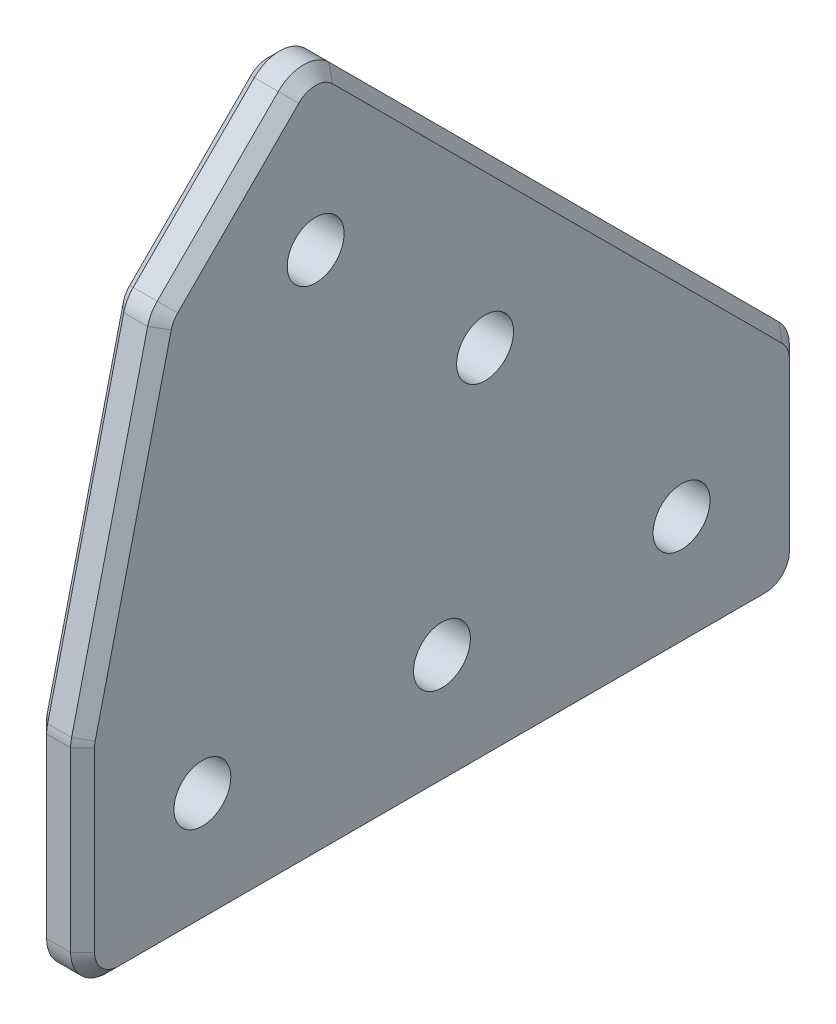
SolidWorks part; units mm, degrees
material "Chrome Stainless Steel"
ref_plane "Front Plane" through (0, 0, 0) normal (0, 0, 1) x (1, 0, 0)
ref_plane "Top Plane" through (0, 0, 0) normal (0, 1, 0) x (1, 0, 0)
ref_plane "Right Plane" through (0, 0, 0) normal (1, 0, 0) x (0, 0, -1)
sketch "Sketch1" plane through (0, 0, 0) normal (1, 0, 0) x (0, 0, -1)
  line L0 (0, 0) -> (-350, 350) construction
  line L1 (-350, 350) -> (-350, 0) construction
  line L2 (-350, 0) -> (0, 0) construction
  line L3 (-78.1401, 0) -> (-18.1401, 0)
  line L4 (-18.1401, 0) -> (-18.1401, 18.1401)
  line L5 (-18.1401, 18.1401) -> (-58.6831, 58.6831)
  line L6 (-58.6831, 58.6831) -> (-71.5101, 45.8561)
  line L7 (-78.1401, 0) -> (-78.1401, 18.1401)
  line L8 (-78.1401, 18.1401) -> (-71.5101, 45.8561)
  dimension "D1" = 350
  dimension "D2" = 350
  dimension "D3" = 60
extrude "Boss-Extrude1" add sketch "Sketch1" along normal blind 4
sketch "Sketch2" plane through (4, 0, 0) normal (1, 0, 0) x (0, 0, -1)
  line L0 (-78.1401, 0) -> (-18.1401, 0) construction
  line L1 (-18.1401, 18.1401) -> (-58.6831, 58.6831) construction
  line L2 (-58.6831, 58.6831) -> (-71.5101, 45.8561) construction
  line L5 (-18.1401, 0) -> (-18.1401, 18.1401) construction
  circle A0 centre (-28.1401, 10) radius 2.375
  circle A1 centre (-58.6831, 44.5409) radius 2.375
  dimension "D1" = 4.75
  dimension "D3" = 4.75
  dimension "D2" = 10
  dimension "D4" = 10
  dimension "D5" = 10
  dimension "D6" = 10
extrude "Cut-Extrude1" cut sketch "Sketch2" against normal through all contours A0 region at (4, 10, 28.1401)
pattern_linear "LPattern1" count 3 spacing 20 along (0, 0, 1) of "Cut-Extrude1"
extrude "Cut-Extrude2" cut sketch "Sketch2<4>" against normal through all contours A1 region at (4, 44.5409, 58.6831)
sketch "Sketch2<4>" plane through (4, 0, 0) normal (1, 0, 0) x (0, 0, -1) same geometry as "Sketch2"
pattern_linear "LPattern2" count 2 spacing 20 along (0, -0.7071, -0.7071) of "Cut-Extrude2"
fillet "Fillet1" radius 3 6 edges at (2, 0, 18.1401) (2, 18.1401, 18.1401) (2, 58.6831, 58.6831) (2, 0, 78.1401) (2, 18.1401, 78.1401) (2, 45.8561, 71.5101)
chamfer "Chanfro1" distance 1 angle 45 24 edges at (4, 0, 48.1401) (4, 0.8787, 19.0188) (4, 0.8787, 77.2614) (4, 9.9487, 18.1401) (4, 10.3931, 78.1401) (4, 18.0455, 18.3685) (4, 18.1377, 78.1195) (4, 37.7903, 37.7903) (4, 31.7581, 74.8825) (4, 45.7988, 71.4076) (4, 57.4404, 58.6831) (4, 51.5085, 65.8576) (0, 0, 48.1401) (0, 0.8787, 19.0188) (0, 0.8787, 77.2614) (0, 9.9487, 18.1401) (0, 10.3931, 78.1401) (0, 18.0455, 18.3685) (0, 18.1377, 78.1195) (0, 37.7903, 37.7903) (0, 31.7581, 74.8825) (0, 57.4404, 58.6831) (0, 45.7988, 71.4076) (0, 51.5085, 65.8576)
sketch "Esboço1" plane through (4, 0, 0) normal (1, 0, 0) x (0, 0, -1)
  line L0 (-68.1401, 10) -> (-28.1401, 10) construction
  line L1 (-58.6831, 44.5409) -> (-48.7568, 33.3153) construction
  line L2 (-57.2167, 39.1834) -> (-50.5924, 31.6921)
  line L3 (-63.1401, 13) -> (-53.1401, 13)
  line L4 (-63.1401, 13) -> (-63.1401, 7)
  line L5 (-63.1401, 7) -> (-53.1401, 7)
  line L6 (-53.1401, 13) -> (-53.1401, 7)
  line L7 (-63.1401, 13) -> (-53.1401, 7) construction
  line L8 (-63.1401, 7) -> (-53.1401, 13) construction
  line L9 (-43.1401, 13) -> (-33.1401, 13)
  line L10 (-43.1401, 13) -> (-43.1401, 7)
  line L11 (-43.1401, 7) -> (-33.1401, 7)
  line L12 (-33.1401, 13) -> (-33.1401, 7)
  line L13 (-43.1401, 13) -> (-33.1401, 7) construction
  line L14 (-43.1401, 7) -> (-33.1401, 13) construction
  line L15 (-57.2167, 39.1834) -> (-52.7219, 43.1579)
  line L16 (-50.5924, 31.6921) -> (-46.0977, 35.6666)
  line L17 (-52.7219, 43.1579) -> (-46.0977, 35.6666)
  line L18 (-57.2167, 39.1834) -> (-46.0977, 35.6666) construction
  line L19 (-50.5924, 31.6921) -> (-52.7219, 43.1579) construction
  circle A0 centre (-68.1401, 10) radius 2.375 construction
  circle A2 centre (-48.1401, 10) radius 2.375 construction
  circle A4 centre (-44.5409, 30.3988) radius 2.375 construction
  point P5 (-58.1401, 10)
  point P11 (-38.1401, 10)
  point P17 (-51.6572, 37.425)
  point P18 (-36.1829, 20.4417)
  dimension "D5" = 10
  dimension "D1" = 6
  dimension "D2" = 6
  dimension "D4" = 6
  dimension "D7" = 10
  dimension "D8" = 10
  dimension "D9" = 5
  dimension "D10" = 5
  dimension "D11" = 13
  dimension "D12" = 10
extrude "Ressalto-extrusão1" add sketch "Esboço1" against normal blind 2 from surface starting at face at (0, 23.4465, 53.6579)
equation "\"D1@Sketch2\"=\"D3@Sketch2\""
equation "\"D2@Esboço1\"=\"D1@Esboço1\""
equation "\"D4@Esboço1\"=\"D1@Esboço1\""
